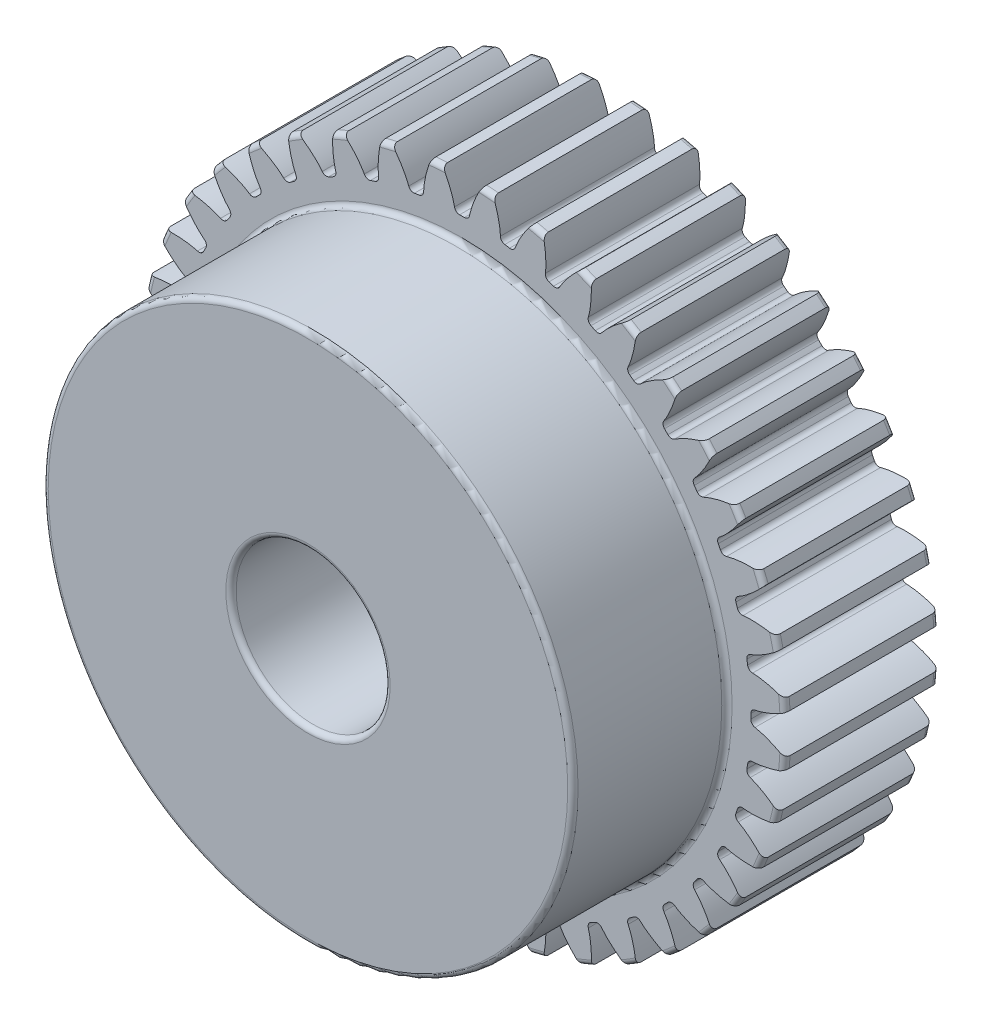
SolidWorks part; units mm, degrees
ref_plane "Front Plane" through (0, 0, 0) normal (0, 0, 1) x (1, 0, 0)
ref_plane "Top Plane" through (0, 0, 0) normal (0, 1, 0) x (1, 0, 0)
ref_plane "Right Plane" through (0, 0, 0) normal (1, 0, 0) x (0, 0, -1)
sketch "Sketch1" plane through (0, 0, 0) normal (0, 0, 1) x (1, 0, 0)
  line L0 (0, 0) -> (0, 25.4) construction
  line L1 (-8.1634, 28.3712) -> (8.1634, 22.4288) construction
  circle A0 centre (0, 0) radius 23.8125 construction
  circle A1 centre (0, 0) radius 26.67 construction
  circle A2 centre (0, 0) radius 25.4 construction
  circle A3 centre (0, 0) radius 23.8682 construction
  circle A4 centre (0, 0) radius 6.35 construction
  circle A5 centre (0, 0) radius 21.844 construction
  point P8 (254, 0)
  point P13 (508, 0)
  point P14 (0, 0)
  dimension "OD | Outside Diameter" = 53.34
  dimension "Root Diameter" = 47.625
  dimension "Gear Pitch Diameter" = 50.8
  dimension "Base Diameter" = 47.7364
  dimension "For Shaft Diameter" = 12.7
  dimension "Hub Diameter" = 43.688
  dimension "Pressure Angle" = 20
  dimension "Number of Teeth" = 1016
  dimension "Gear Pitch | Diametral Pitch" = 508
sketch "Sketch2" plane through (0, 0, 0) normal (1, 0, 0) x (0, 0, -1)
  line L0 (-12.7, 0) -> (12.7, 0) construction
  line L1 (-12.7, 26.67) -> (12.7, 26.67) construction
  point P2 (0, 26.67)
  point P4 (0, 0)
  point P6 (0, 26.67)
  dimension "Overall Width" = 25.4
  dimension "Hub Width" = 12.7
  dimension "Face Width" = 12.7
sketch "Sketch3" plane through (0, 0, 0) normal (0, 0, 1) x (1, 0, 0)
  circle A0 centre (0, 0) radius 26.67
  circle A1 centre (0, 0) radius 26.67 construction
extrude "Boss-Extrude1" add sketch "Sketch3" against normal up to vertex (12.7 mm away) and the other way up to vertex (12.7 mm away) up to point (0, 0, -12.7) other way up to point (0, 0, 12.7)
sketch "Sketch5" plane through (0, 0, 0) normal (1, 0, 0) x (0, 0, -1)
  line L1 (-12.7, 26.67) -> (0, 26.67)
  line L2 (-12.7, 26.67) -> (-12.7, 21.844)
  line L3 (-12.7, 21.844) -> (0, 21.844)
  line L4 (0, 26.67) -> (0, 21.844)
  line L11 (12.7, 6.35) -> (-12.7, 6.35)
  line L12 (12.7, 6.35) -> (12.7, 0)
  line L13 (12.7, 0) -> (-12.7, 0)
  line L14 (-12.7, 6.35) -> (-12.7, 0)
  point P5 (0, 6.35)
  point P12 (0, 21.844)
revolve "Cut-Revolve1" cut sketch "Sketch5" angle 360 about L0
fillet "Fillet2" radius 0.4261 6 edges at (26.67, 0, -12.7) (6.35, 0, -12.7) (6.35, 0, 12.7) (21.844, 0, 0) (26.67, 0, 0) (21.844, 0, 12.7)
sketch "Sketch4" plane through (0, 0, 0) normal (0, 0, 1) x (1, 0, 0)
  line L0 (0, 0) -> (23.8054, 0.5801) construction
  line L2 (0, 0) -> (23.8054, -0.5801) construction
  line L4 (23.8054, 0.5801) -> (23.8611, 0.5815)
  line L5 (23.8611, -0.5815) -> (23.8054, -0.5801)
  arc A0 (23.8054, 0.5801) -> (23.8054, -0.5801) centre (0, 0) cw
  arc A3 (26.6213, 1.6107) -> (26.6213, -1.6107) centre (0, 0) cw
  circle A4 centre (0, 0) radius 26.67 construction
  spline S0 degree 4 poles (23.8611, 0.5815) (23.8655, 0.5817) (23.8778, 0.5822) (23.901, 0.5839) (23.9389, 0.5874) (23.9871, 0.593) (24.0493, 0.6016) (24.1225, 0.6136) (24.2029, 0.6285) (24.2903, 0.6467) (24.3773, 0.6666) (24.464, 0.6881) (24.5503, 0.711) (24.6546, 0.7404) (24.7796, 0.7781) (24.9253, 0.8257) (25.0903, 0.8838) (25.2579, 0.9474) (25.4225, 1.0136) (25.5884, 1.0847) (25.7486, 1.1565) (25.9145, 1.2353) (26.0673, 1.3103) (26.238, 1.3989) (26.3756, 1.4719) (26.5565, 1.5732) (26.6631, 1.6345) (26.7877, 1.708) (26.8429, 1.7415) (26.8769, 1.7622) knots 0 0 0 0 0 0.005377 0.015084 0.028532 0.04661 0.064855 0.092111 0.119476 0.146842 0.174209 0.201575 0.228941 0.256307 0.307035 0.361767 0.4165 0.471232 0.525964 0.580697 0.635429 0.690161 0.744894 0.799626 0.854358 0.909091 0.954545 1 1 1 1 1 construction
  spline S1 degree 4 poles (23.8611, 0.5815) (23.8655, 0.5817) (23.8778, 0.5822) (23.901, 0.5839) (23.9389, 0.5874) (23.9871, 0.593) (24.0493, 0.6016) (24.1225, 0.6136) (24.2029, 0.6285) (24.2903, 0.6467) (24.3773, 0.6666) (24.464, 0.6881) (24.5503, 0.711) (24.6546, 0.7404) (24.7796, 0.7781) (24.9253, 0.8257) (25.0903, 0.8838) (25.2579, 0.9474) (25.4225, 1.0136) (25.5884, 1.0847) (25.7486, 1.1565) (25.9145, 1.2353) (26.0673, 1.3103) (26.238, 1.3989) (26.3756, 1.4719) (26.5173, 1.5512) (26.5862, 1.5904) (26.6213, 1.6107) knots 0 0 0 0 0 0.005377 0.015084 0.028532 0.04661 0.064855 0.092111 0.119476 0.146842 0.174209 0.201575 0.228941 0.256307 0.307035 0.361767 0.4165 0.471232 0.525964 0.580697 0.635429 0.690161 0.744894 0.799626 0.854358 0.909091 0.909091 0.909091 0.909091 0.909091
  spline S2 degree 4 poles (23.8611, -0.5815) (23.8655, -0.5817) (23.8778, -0.5822) (23.901, -0.5839) (23.9389, -0.5874) (23.9871, -0.593) (24.0493, -0.6016) (24.1225, -0.6136) (24.2029, -0.6285) (24.2903, -0.6467) (24.3773, -0.6666) (24.464, -0.6881) (24.5503, -0.711) (24.6546, -0.7404) (24.7796, -0.7781) (24.9253, -0.8257) (25.0903, -0.8838) (25.2579, -0.9474) (25.4225, -1.0136) (25.5884, -1.0847) (25.7486, -1.1565) (25.9145, -1.2353) (26.0673, -1.3103) (26.238, -1.3989) (26.3756, -1.4719) (26.5565, -1.5732) (26.6631, -1.6345) (26.7877, -1.708) (26.8429, -1.7415) (26.8769, -1.7622) knots 0 0 0 0 0 0.005377 0.015084 0.028532 0.04661 0.064855 0.092111 0.119476 0.146842 0.174209 0.201575 0.228941 0.256307 0.307035 0.361767 0.4165 0.471232 0.525964 0.580697 0.635429 0.690161 0.744894 0.799626 0.854358 0.909091 0.954545 1 1 1 1 1 construction
  spline S3 degree 4 poles (23.8611, -0.5815) (23.8655, -0.5817) (23.8778, -0.5822) (23.901, -0.5839) (23.9389, -0.5874) (23.9871, -0.593) (24.0493, -0.6016) (24.1225, -0.6136) (24.2029, -0.6285) (24.2903, -0.6467) (24.3773, -0.6666) (24.464, -0.6881) (24.5503, -0.711) (24.6546, -0.7404) (24.7796, -0.7781) (24.9253, -0.8257) (25.0903, -0.8838) (25.2579, -0.9474) (25.4225, -1.0136) (25.5884, -1.0847) (25.7486, -1.1565) (25.9145, -1.2353) (26.0673, -1.3103) (26.238, -1.3989) (26.3756, -1.4719) (26.5173, -1.5512) (26.5862, -1.5904) (26.6213, -1.6107) knots 0 0 0 0 0 0.005377 0.015084 0.028532 0.04661 0.064855 0.092111 0.119476 0.146842 0.174209 0.201575 0.228941 0.256307 0.307035 0.361767 0.4165 0.471232 0.525964 0.580697 0.635429 0.690161 0.744894 0.799626 0.854358 0.909091 0.909091 0.909091 0.909091 0.909091
  dimension "D1" = 47.625
extrude "Cut-Extrude1" cut sketch "Sketch4" against normal through all both and the other way through all
fillet "Fillet1" radius 0.4261 2 edges at (23.8054, -0.5801, -6.35) (23.8054, 0.5801, -6.35)
pattern_circular "CirPattern1" count 40 over 360 about axis through (0, 0, 12.7) along (0, 0, -1) of "Cut-Extrude1", "Fillet1"
equation "\"Root Diameter@Sketch1\"=\"Root Diameter\""
equation "\"OD | Outside Diameter@Sketch1\"=\"Outside Diameter\""
equation "\"D1@CirPattern1\"=\"Number of Teeth\""
equation "\"Diametral Pitch\"=20"
equation "\"Number of Teeth\"= 40"
equation "\"Pressure Angle\"=20"
equation "\"Pitch Diameter\"= \"Number of Teeth\" / \"Diametral Pitch\""
equation "\"Base Diameter\"= \"Pitch Diameter\" * cos ( \"Pressure Angle\" )"
equation "\"Outside Diameter\"= ( \"Number of Teeth\" + 2 ) / \"Diametral Pitch\""
equation "\"Dedendum\"= 1.25 / \"Diametral Pitch\""
equation "\"Root Diameter\"= \"Pitch Diameter\" - ( 2 * \"Dedendum\" )"
equation "\"Pitch Angle\"= 360deg / \"Number of Teeth\""
equation "\"Alpha\"= sqr ( \"Pitch Diameter\" ^ 2 - \"Base Diameter\" ^ 2 ) / \"Base Diameter\" * 180 / PI - \"Pressure Angle\""
equation "\"Beta\"= ( \"Pitch Angle\" / 4 - \"Alpha\" )"
equation "\"Phi\"= sqr ( ( \"Outside Diameter\" / 2 ) ^ 2 - ( \"Base Diameter\" / 2 ) ^ 2 ) / ( \"Base Diameter\" / 2 )"
equation "\"Addendum\"= 1 / \"Diametral Pitch\""
equation "\"WorkingDepth\"= 2 / \"Diametral Pitch\""
equation "\"WholeDepth\"= 2.25 / \"Diametral Pitch\""
equation "\"Clearance\"= 0.25 / \"Diametral Pitch\""
equation "\"ToothThickness\"= ( pi * 2 ) / \"Diametral Pitch\""
equation "\"CircularPitch\"= pi / \"Diametral Pitch\""
equation "\"Number of Teeth@Sketch1\"=\"Number of Teeth\""
equation "\"Gear Pitch | Diametral Pitch@Sketch1\"=\"Diametral Pitch\""
equation "\"Pressure Angle@Sketch1\"=\"Pressure Angle\""
equation "\"Gear Pitch Diameter@Sketch1\"=\"Pitch Diameter\""
equation "\"Base Diameter@Sketch1\"=\"Base Diameter\""
equation "\"Fillet\"= \"Clearance\" * cos ( \"Pressure Angle\" ) * tan ( ( 90 + \"Pressure Angle\" ) / 2 )"
equation "\"D1@Fillet1\"=\"Fillet\""
equation "\"D1@Sketch4\"=if( \"Base Diameter\">\"Root Diameter\",\"Root Diameter\",\"Base Diameter\"-.00001)"
equation "\"D1@Fillet2\"=\"Fillet\""
